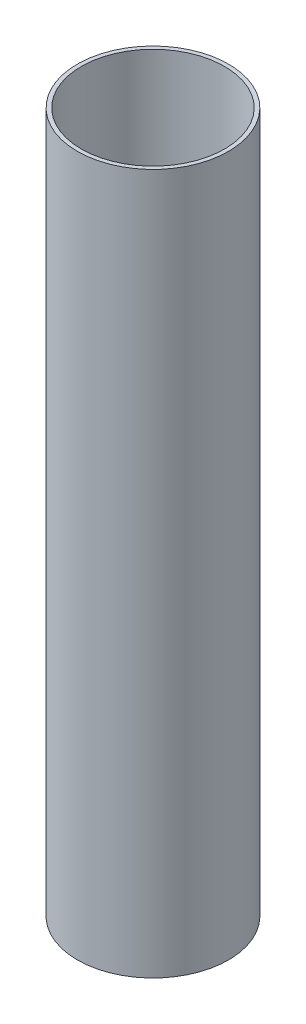
SolidWorks part; units mm, degrees
material "Epoxy, Unfilled"
ref_plane "Front Plane" through (0, 0, 0) normal (0, 0, 1) x (1, 0, 0)
ref_plane "Top Plane" through (0, 0, 0) normal (0, 1, 0) x (1, 0, 0)
ref_plane "Right Plane" through (0, 0, 0) normal (1, 0, 0) x (0, 0, -1)
sketch "Sketch2" plane through (0, 0, 0) normal (0, 1, 0) x (1, 0, 0)
  circle A0 centre (0, 0) radius 60.325
  circle A1 centre (0, 0) radius 57.15
extrude "Boss-Extrude1" add sketch "Sketch2" along normal blind 558.8
